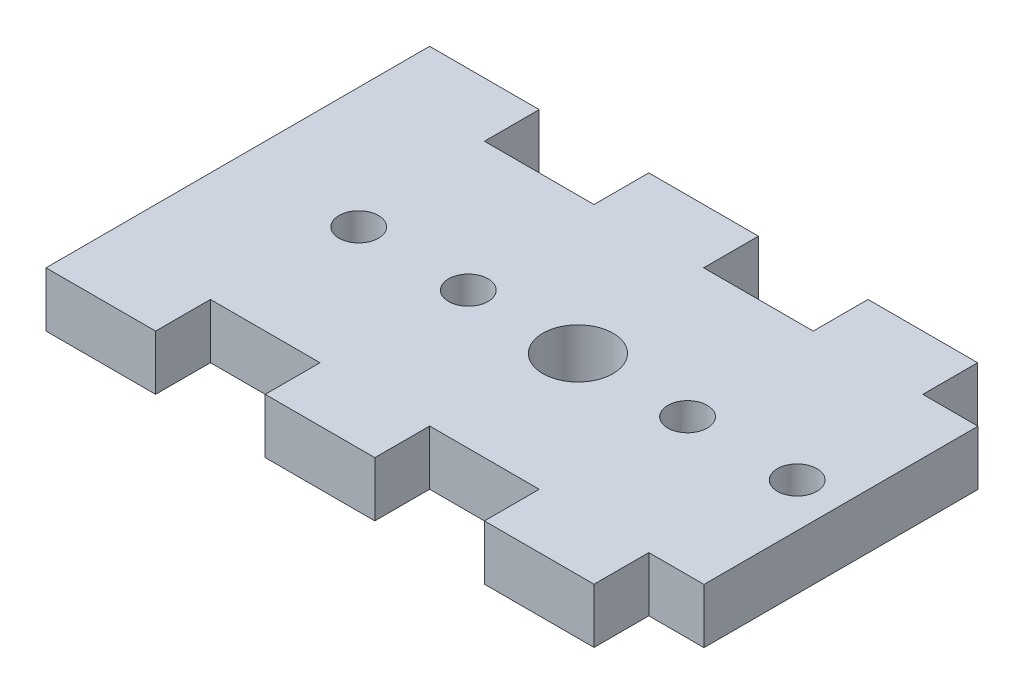
SolidWorks part; units mm, degrees
material "Custom Plastic"
ref_plane "Front Plane" through (0, 0, 0) normal (0, 0, 1) x (1, 0, 0)
ref_plane "Top Plane" through (0, 0, 0) normal (0, 1, 0) x (1, 0, 0)
ref_plane "Right Plane" through (0, 0, 0) normal (1, 0, 0) x (0, 0, -1)
sketch "Sketch1" plane through (0, 0, 0) normal (0, 1, 0) x (1, 0, 0)
  line L0 (-43.18, 15.875) -> (-37.7698, 15.875)
  line L1 (43.18, -22.225) -> (-43.18, -22.225) construction
  line L2 (43.18, -22.225) -> (43.18, 22.225) construction
  line L3 (43.18, 22.225) -> (-43.18, 22.225) construction
  line L4 (-43.18, -22.225) -> (-43.18, 22.225) construction
  line L5 (43.18, -22.225) -> (-43.18, 22.225) construction
  line L6 (43.18, 22.225) -> (-43.18, -22.225) construction
  line L7 (-37.7698, 15.875) -> (-37.7698, 22.225)
  line L8 (-37.7698, 22.225) -> (-25.0698, 22.225)
  line L9 (-25.0698, 22.225) -> (-25.0698, 15.875)
  line L10 (-25.0698, 15.875) -> (-12.3698, 15.875)
  line L11 (-12.3698, 15.875) -> (-12.3698, 22.225)
  line L12 (-12.3698, 22.225) -> (0.3302, 22.225)
  line L13 (0.3302, 22.225) -> (0.3302, 15.875)
  line L14 (0.3302, 15.875) -> (13.0302, 15.875)
  line L15 (13.0302, 15.875) -> (13.0302, 22.225)
  line L16 (13.0302, 22.225) -> (25.7302, 22.225)
  line L17 (25.7302, 22.225) -> (25.7302, 15.875)
  line L18 (25.7302, 15.875) -> (43.18, 15.875)
  line L19 (-43.18, 15.875) -> (-43.18, -15.875)
  line L20 (-43.18, -15.875) -> (-37.7698, -15.875)
  line L21 (-37.7698, -15.875) -> (-37.7698, -22.225)
  line L22 (-37.7698, -22.225) -> (-25.0698, -22.225)
  line L23 (-25.0698, -22.225) -> (-25.0698, -15.875)
  line L24 (-25.0698, -15.875) -> (-12.3698, -15.875)
  line L25 (-12.3698, -15.875) -> (-12.3698, -22.225)
  line L26 (-12.3698, -22.225) -> (0.3302, -22.225)
  line L27 (0.3302, -22.225) -> (0.3302, -15.875)
  line L28 (0.3302, -15.875) -> (13.0302, -15.875)
  line L29 (13.0302, -15.875) -> (13.0302, -22.225)
  line L30 (13.0302, -22.225) -> (25.7302, -22.225)
  line L31 (25.7302, -22.225) -> (25.7302, -15.875)
  line L32 (25.7302, -15.875) -> (43.18, -15.875)
  line L33 (43.18, 15.875) -> (43.18, -15.875)
  point P0 (0, 0)
  dimension "D1" = 44.45
  dimension "D2" = 86.36
  dimension "D3" = 12.7
  dimension "D4" = 6.35
  dimension "D5" = 5.4102
extrude "Main" add sketch "Sketch1" along normal blind 6.35
sketch "Sketch3" plane through (0, 6.35, 0) normal (0, 1, 0) x (1, 0, 0)
  line L0 (-43.18, 15.875) -> (-43.18, -15.875) construction
  line L1 (-23.7584, 0) -> (-11.0584, 0) construction
  line L2 (-11.0584, 0) -> (1.6416, 0) construction
  line L3 (1.6416, 0) -> (14.3416, 0) construction
  line L4 (14.3416, 0) -> (27.0416, 0) construction
  line L5 (1.6416, 0) -> (1.6416, 15.875) construction
  line L6 (13.0302, 15.875) -> (0.3302, 15.875) construction
  line L7 (1.6416, 0) -> (1.6416, -15.875) construction
  line L8 (0.3302, -15.875) -> (13.0302, -15.875) construction
  circle A1 centre (1.6416, 0) radius 4.064
  circle A3 centre (14.3416, 0) radius 2.286
  circle A5 centre (27.0416, 0) radius 2.286
  circle A7 centre (-11.0584, 0) radius 2.286
  circle A9 centre (-23.7584, 0) radius 2.286
  dimension "D1" = 8.128
  dimension "D4" = 4.572
  dimension "D2" = 19.4216
  dimension "D3" = 12.7
extrude "Gear Mount Holes" cut sketch "Sketch3" against normal through all
sketch "Sketch4" plane through (0, 6.35, 0) normal (0, 1, 0) x (1, 0, 0)
  line L0 (25.7302, -15.875) -> (43.18, -15.875) construction
  line L1 (43.18, 15.875) -> (32.1216, 15.875)
  line L2 (43.18, 15.875) -> (43.18, -15.875)
  line L3 (43.18, -15.875) -> (32.1216, -15.875)
  line L4 (32.1216, 15.875) -> (32.1216, -15.875)
  line L5 (-43.18, 15.875) -> (-37.7698, 15.875)
  line L6 (-37.7698, 15.875) -> (-37.7698, -15.875)
  line L7 (-37.7698, -15.875) -> (-43.18, -15.875)
  line L8 (-43.18, -15.875) -> (-43.18, 15.875)
  circle A0 centre (27.0416, 0) radius 2.286 construction
  dimension "D1" = 5.08
extrude "Cut-Extrude2" cut sketch "Sketch4" against normal through all
